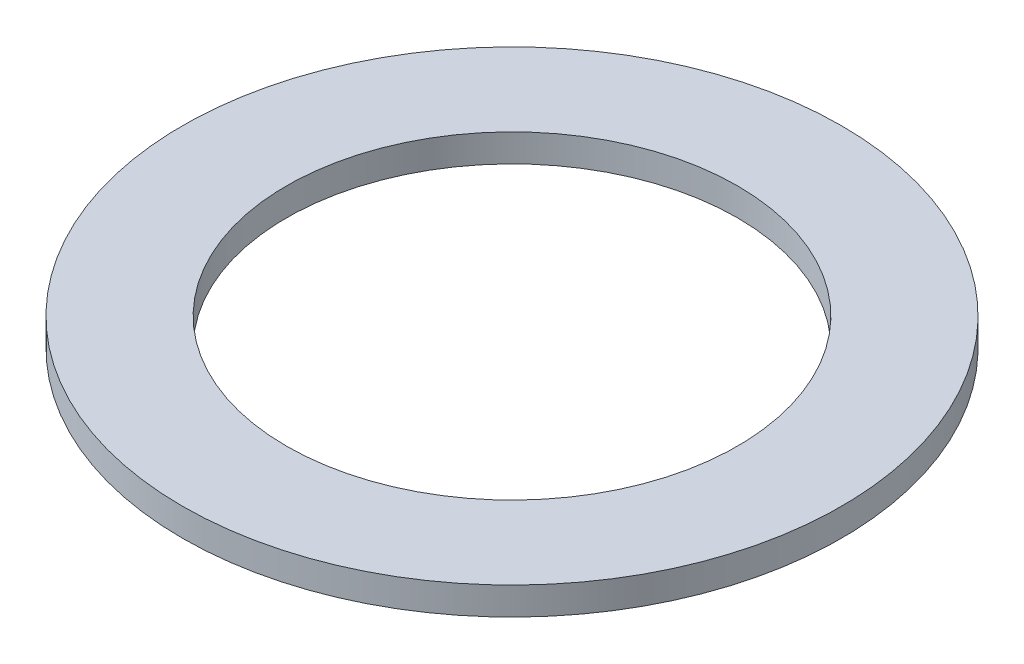
SolidWorks part; units mm, degrees
ref_plane "Front Plane" through (0, 0, 0) normal (0, 0, 1) x (1, 0, 0)
ref_plane "Top Plane" through (0, 0, 0) normal (0, 1, 0) x (1, 0, 0)
ref_plane "Right Plane" through (0, 0, 0) normal (1, 0, 0) x (0, 0, -1)
sketch "Sketch1" plane through (0, 0, 0) normal (0, 1, 0) x (1, 0, 0)
  circle A0 centre (0, 0) radius 47.5
  dimension "FLANGE_OD" = 95
extrude "Boss-Extrude1" add sketch "Sketch1" along normal blind 4
sketch "Sketch2" plane through (0, 0, 0) normal (0, 1, 0) x (1, 0, 0)
  circle A0 centre (0, 0) radius 32.5
  dimension "BORE_D" = 65
extrude "Cut-Extrude1" cut sketch "Sketch2" along normal through all
sketch "Sketch3" plane through (0, 4, 0) normal (0, 1, 0) x (1, 0, 0)
  circle A0 centre (0, 0) radius 19.8571 construction
  circle A1 centre (-19.8571, 0) radius 1.8208
  dimension "BOLT_D" = 3.6416
  dimension "BOLT_PCD" = 39.7142
extrude "Cut-Extrude2" cut sketch "Sketch3" against normal blind 3.945 rebuild error yes
pattern_circular "CirPattern1" count 6 over 360 rebuild error yes
